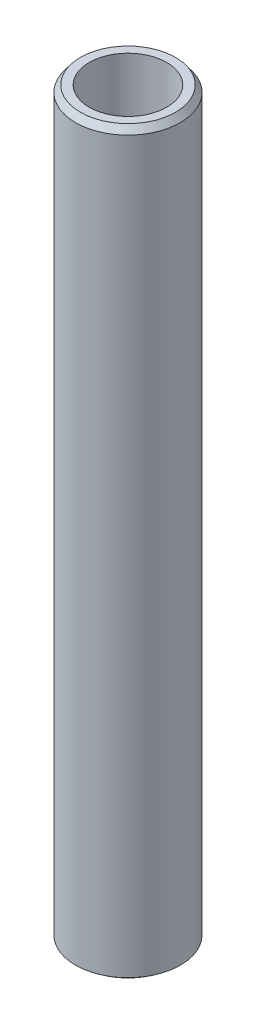
SolidWorks part; units mm, degrees
ref_plane "Front Plane" through (0, 0, 0) normal (0, 0, 1) x (1, 0, 0)
ref_plane "Top Plane" through (0, 0, 0) normal (0, 1, 0) x (1, 0, 0)
ref_plane "Right Plane" through (0, 0, 0) normal (1, 0, 0) x (0, 0, -1)
sketch "Sketch1" plane through (0, 0, 0) normal (0, 1, 0) x (1, 0, 0)
  circle A0 centre (0, 0) radius 15
  dimension "SHAFT_OD" = 30
extrude "Boss-Extrude1" add sketch "Sketch1" along normal blind 212.0516
sketch "Sketch2" plane through (0, 0, 0) normal (0, 1, 0) x (1, 0, 0)
  circle A0 centre (0, 0) radius 11.0973
  dimension "BORE_D" = 22.1947
extrude "Cut-Extrude1" cut sketch "Sketch2" along normal through all
chamfer "Chamfer1" distance 1.8727 angle 36.64 2 edges at (0, 212.0516, 15) (0, 0, 15) first distance on face at (0, 212.0516, 15) first distance on face at (0, 0, 11.0973)
